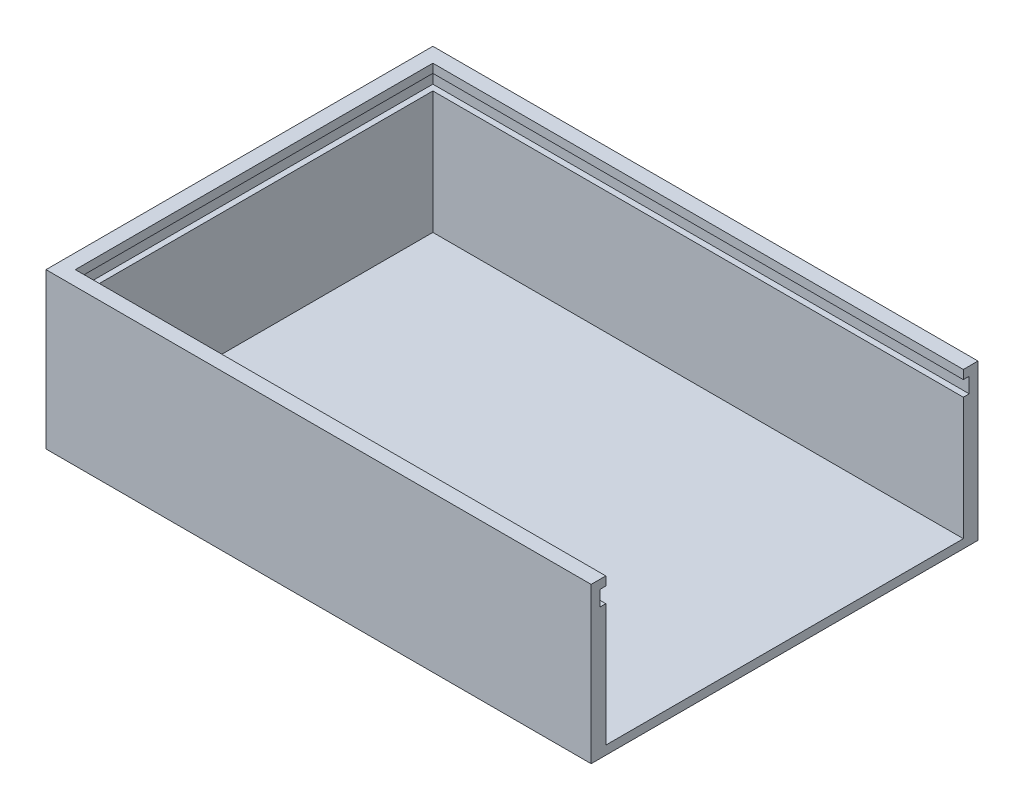
SolidWorks part; units mm, degrees
ref_plane "Front" through (0, 0, 0) normal (0, 0, 1) x (1, 0, 0)
ref_plane "Top" through (0, 0, 0) normal (0, 1, 0) x (1, 0, 0)
ref_plane "Right" through (0, 0, 0) normal (1, 0, 0) x (0, 0, -1)
sketch "Esquisse1" plane through (0, 0, 0) normal (0, 1, 0) x (1, 0, 0)
  line L1 (-93, 66) -> (93, 66)
  line L2 (-93, 66) -> (-93, -66)
  line L3 (-93, -66) -> (93, -66)
  line L4 (93, 66) -> (93, -66)
  line L5 (-93, 66) -> (93, -66) construction
  line L6 (-93, -66) -> (93, 66) construction
  point P0 (0, 0)
  dimension "D1" = 186
  dimension "D2" = 132
extrude "Boss.-Extru.1" add sketch "Esquisse1" along normal blind 3
sketch "Esquisse4" plane through (0, 3, 0) normal (0, 1, 0) x (1, 0, 0)
  line L0 (-93, 66) -> (-93, -66) construction
  line L1 (93, 66) -> (-93, 66)
  line L2 (93, 66) -> (93, 61)
  line L3 (93, 61) -> (-93, 61)
  line L4 (-93, 66) -> (-93, 61)
  line L6 (93, -66) -> (-93, -66)
  line L7 (93, -66) -> (93, -61)
  line L8 (93, -61) -> (-93, -61)
  line L9 (-93, -66) -> (-93, -61)
  line L10 (-93, -61) -> (-88, -61)
  line L11 (-93, -61) -> (-93, 61)
  line L12 (-93, 61) -> (-88, 61)
  line L13 (-88, -61) -> (-88, 61)
  line M9 (93, -66) -> (93, 66)
  line M10 (93, 66) -> (-93, 66)
  line M11 (-93, 66) -> (-93, -66)
  line M12 (-93, -66) -> (93, -66)
  dimension "D1" = 5
  dimension "D2" = 5
  dimension "D3" = 5
extrude "Boss.-Extru.4" add sketch "Esquisse4" along normal blind 50 contours L3 M9 M10 M11 | L8 L13 L3 M11 | L8 M9 M11 M12 region at (0, 3, -63.5) region at (-90.5, 3, 0) region at (0, 3, 63.5)
sketch "Esquisse5" plane through (93, 0, 0) normal (1, 0, 0) x (0, 0, -1)
  line L0 (-61, 53) -> (-61, 3) construction
  line L1 (-63, 50) -> (63, 50)
  line L2 (-63, 50) -> (-63, 44.8)
  line L3 (-63, 44.8) -> (63, 44.8)
  line L4 (63, 50) -> (63, 44.8)
  line L5 (61, 53) -> (61, 3) construction
  line L6 (61, 53) -> (66, 53) construction
  dimension "D1" = 2
  dimension "D2" = 2
  dimension "D3" = 3
  dimension "D4" = 5.2
extrude "Enlèv. mat.-Extru.1" cut sketch "Esquisse5" against normal blind 183
